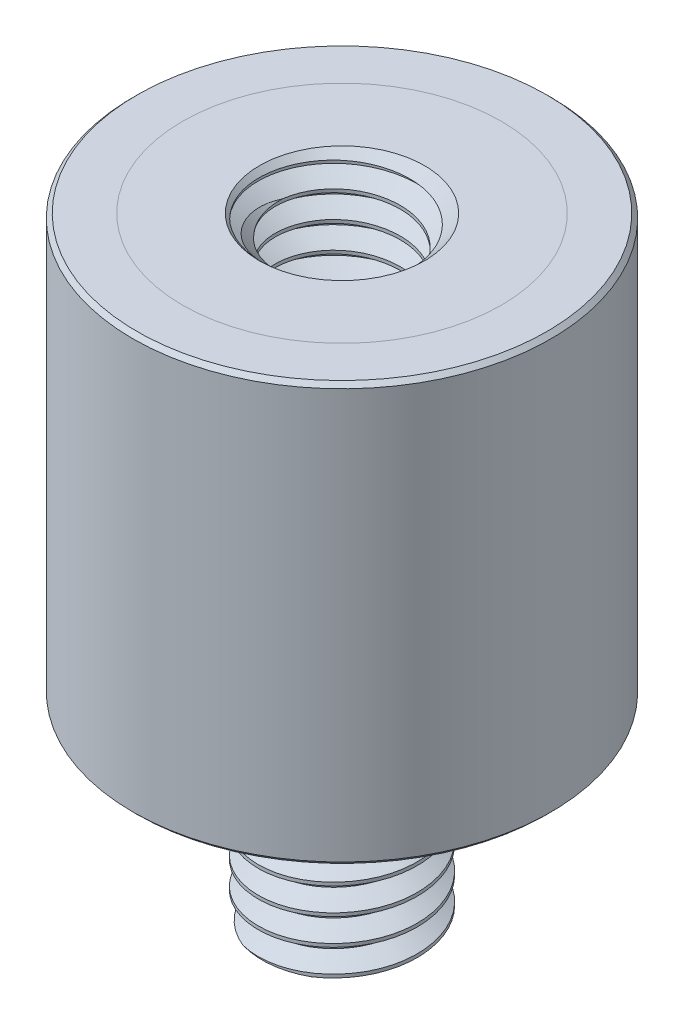
SolidWorks part; units mm, degrees
ref_plane "Front Plane" through (0, 0, 0) normal (0, 0, 1) x (1, 0, 0)
ref_plane "Top Plane" through (0, 0, 0) normal (0, 1, 0) x (1, 0, 0)
ref_plane "Right Plane" through (0, 0, 0) normal (1, 0, 0) x (0, 0, -1)
sketch "Sketch1" plane through (0, 0, 0) normal (1, 0, 0) x (0, 0, -1)
  line L0 (0, 0) -> (0, -6.096) construction
  line L1 (-3.937, 7.874) -> (3.937, 7.874) construction
  line L2 (-3.937, 7.874) -> (-3.937, 0) construction
  line L3 (-3.937, 0) -> (3.937, 0) construction
  line L4 (3.937, 7.874) -> (3.937, 0) construction
  line L5 (-1.5, -6.096) -> (1.5, -6.096) construction
  line L6 (-1.5, 7.874) -> (-1.5, 4.826) construction
  line L7 (-1.5, 4.826) -> (1.5, 4.826) construction
  line L8 (1.5, 4.826) -> (1.5, 7.874) construction
  line L9 (-1.5541, -6.0648) -> (-1.5541, -6.5648) construction
  line L10 (-1.5541, -6.5648) -> (-1.1211, -6.3148) construction
  line L11 (-1.1211, -6.3148) -> (-1.5541, -6.0648) construction
  line L12 (-1.5271, -6.0804) -> (-1.5271, -6.5491) construction
  line L13 (-1.5, -6.096) -> (-1.5, -6.5335) construction
  line L14 (-1.1752, -6.2835) -> (-1.1752, -6.346) construction
  line L15 (-1.1752, -6.3148) -> (-1.1211, -6.3148) construction
  line L16 (-1.5541, -6.3148) -> (-1.5, -6.3148) construction
  line L17 (-1.5541, 8.3427) -> (-1.5541, 7.8428) construction
  line L18 (-1.5541, 7.8428) -> (-1.1211, 8.0927) construction
  line L19 (-1.1211, 8.0927) -> (-1.5541, 8.3427) construction
  line L20 (-1.5271, 8.3271) -> (-1.5271, 7.8584) construction
  line L21 (-1.5, 8.3115) -> (-1.5, 7.874) construction
  line L22 (-1.1752, 8.124) -> (-1.1752, 8.0615) construction
  line L23 (-1.1752, 8.0927) -> (-1.1211, 8.0927) construction
  line L24 (-1.5541, 8.0927) -> (-1.5, 8.0927) construction
  point P4 (0, 0)
  point P11 (0, -6.096)
  point P14 (0, 4.826)
  point P28 (-1.5271, -6.3148)
  point P29 (3.937, 1.016)
  point P41 (-1.5271, 8.0927)
  point P42 (-3, 0)
  point P43 (3, 0)
  point P44 (1.5, -4.346)
  point P46 (1.5, 7.874)
  point P47 (3.937, 6.858)
  dimension "Thread OD" = 3
  dimension "Diameter" = 7.874
  dimension "Height" = 7.874
  dimension "Thread length" = 6.096
  dimension "Thread depth" = 3.048
  dimension "D1" = 3
  dimension "D2" = 60
  dimension "Thread Pitch" = 0.5
  dimension "D3" = 0.0625
  dimension "D4" = 0.5
  dimension "D5" = 0.0625
  dimension "D6" = 60
  dimension "Cover Plate Thickness" = 1.016
  dimension "D8" = 1.016
  dimension "Cover Plate Diameter" = 6
  dimension "D10" = 1.75
sketch "Sketch2" plane through (0, 0, 0) normal (0, 1, 0) x (1, 0, 0)
  circle A0 centre (0, 0) radius 3.937 construction
  dimension "D1" = 7.874
sketch "Sketch3" plane through (0, 0, 0) normal (1, 0, 0) x (0, 0, -1)
  line L0 (0, 1.016) -> (0, -6.096)
  line L1 (0, -6.096) -> (-1.15, -6.096)
  line L2 (-1.5, -6.096) -> (1.5, -6.096) construction
  line L3 (-1.15, -6.096) -> (-1.5, -5.746)
  line L4 (-1.5, -5.746) -> (-1.5, 1.016)
  line L5 (-1.5, 1.016) -> (0, 1.016)
  dimension "D1" = 45
  dimension "D2" = 0.35
revolve "Revolve1" add sketch "Sketch3" angle 360 about L0
sketch "Sketch4" plane through (0, 0, 0) normal (1, 0, 0) x (0, 0, -1)
  line L1 (-1.875, 6.858) -> (-1.875, 3.951)
  line L5 (-3, 7.874) -> (-3, 6.858)
  line L6 (-1.5, 7.874) -> (-1.5, 4.826)
  line L7 (-3.937, 7.874) -> (3.937, 7.874) construction
  line L8 (-1.5, 4.826) -> (0, 4.326)
  line L9 (-3, 6.858) -> (-1.875, 6.858)
  line L11 (-3, 7.874) -> (-1.5, 7.874)
  line L13 (0, 7.874) -> (0, 4.826) construction
  line L14 (-1.5, 4.826) -> (1.5, 4.826) construction
  line L15 (0, 4.826) -> (0, 4.326) construction
  line L16 (0, 4.326) -> (0, 3.951)
  line L17 (0, 3.951) -> (-1.875, 3.951)
  line L18 (-1.875, 6.858) -> (-1.5, 6.858) construction
  dimension "D1" = 0.5
  dimension "D2" = 3.75
revolve "Revolve2" add sketch "Sketch4" angle 360 about L13
sketch "Sketch5" plane through (0, 0, 0) normal (1, 0, 0) x (0, 0, -1)
  line L0 (-3, 0) -> (-3, 1.016)
  line L1 (-3, 1.016) -> (-1.5, 1.016)
  line L2 (-1.5, 1.016) -> (-1.5, 0)
  line L3 (-3.937, 0) -> (3.937, 0) construction
  line L4 (-1.5, 0) -> (-3, 0)
revolve "Revolve3" add sketch "Sketch5" angle 360 about L0
sketch "Sketch6" plane through (0, 0, 0) normal (1, 0, 0) x (0, 0, -1)
  line L0 (-3, 7.874) -> (-3.937, 7.874)
  line L1 (-3.937, 7.874) -> (-3.937, 0)
  line L2 (-3.937, 0) -> (-3, 0)
  line L3 (-3, 0) -> (-3, 1.016)
  line L4 (-3, 1.016) -> (0, 1.016)
  line L5 (0, 1.016) -> (0, 3.951)
  line L6 (0, 3.951) -> (-1.875, 3.951)
  line L7 (-1.875, 3.951) -> (-1.875, 6.858)
  line L8 (-1.875, 6.858) -> (-3, 6.858)
  line L9 (-3, 6.858) -> (-3, 7.874)
revolve "Revolve4" add sketch "Sketch6" angle 360 about L5
chamfer "Chamfer1" distance 0.0787 2 edges at (0, 7.874, -3.937) (0, 0, -3.937)
split "Split1" bodies to split 106 resulting bodies 108 109 split by face at (0, 0, -1.5)
sketch "Sketch7" plane through (0, 0, 0) normal (1, 0, 0) x (0, 0, -1)
  line L0 (-1.5271, -6.0804) -> (-1.5271, -6.5491)
  line L1 (-1.5271, -6.5491) -> (-1.1752, -6.346)
  line L2 (-1.1752, -6.346) -> (-1.1752, -6.2835)
  line L3 (-1.1752, -6.2835) -> (-1.5271, -6.0804)
sketch "Sketch8" plane through (0, -6.096, 0) normal (0, -1, 0) x (1, 0, 0)
  line L0 (0, 1.5) -> (0, -1.5) construction
  circle A0 centre (0, 0) radius 1.5
curve "Helix/Spiral1" pitch 0.5 height 6.596 radius 1.5 centre (0, -6.096, 0) axis (0, 1, 0) start towards (0, 0, 1)
sweep "Cut-Sweep1" cut profiles "Sketch7" path "Helix/Spiral1" align with end faces yes
combine bodies "Combine1" operation type add bodies to combine 109 110
sketch "Sketch9" plane through (0, 0, 0) normal (1, 0, 0) x (0, 0, -1)
  line L0 (-1.5271, 8.3271) -> (-1.5271, 7.8584)
  line L1 (-1.5271, 8.3271) -> (-1.1752, 8.124)
  line L2 (-1.1752, 8.124) -> (-1.1752, 8.0615)
  line L3 (-1.1752, 8.0615) -> (-1.5271, 7.8584)
sketch "Sketch10" plane through (0, 7.874, 0) normal (0, 1, 0) x (1, 0, 0)
  line L0 (0, -3.937) -> (0, 3.937) construction
  circle A0 centre (0, 0) radius 1.5
curve "Helix/Spiral2" pitch 0.5 height 3.548 radius 1.5 centre (0, 7.874, 0) axis (0, -1, 0) start towards (0, 0, 1)
sweep "Sweep1" add profiles "Sketch9" path "Helix/Spiral2"
sketch "Sketch11" plane through (0, 7.874, 0) normal (0, 1, 0) x (1, 0, 0)
  line L0 (0, -3.937) -> (0, 3.937) construction
  circle A0 centre (0, 0) radius 1.5541
extrude "Cut-Extrude1" cut sketch "Sketch11" along normal through all and the other way through all draft 45
sketch "Sketch12" plane through (0, -6.096, 0) normal (0, -1, 0) x (1, 0, 0)
  circle A0 centre (0, 0) radius 1.831
extrude "Cut-Extrude2" cut sketch "Sketch12" against normal blind 2.54
equation "\"D1@Sketch1\"=\"Thread OD@Sketch1\""
equation "\"D1@Sketch2\"=\"Diameter@Sketch1\""
equation "\"D3@Sketch1\"=\"Thread Pitch@Sketch1\"/8"
equation "\"D4@Sketch1\"=\"Thread Pitch@Sketch1\""
equation "\"D5@Sketch1\"=\"D4@Sketch1\"/8"
equation "\"D8@Sketch1\"=\"Cover Plate Thickness@Sketch1\""
equation "\"D2@Sketch3\"=\"Thread Pitch@Sketch1\"*.7"
equation "\"D1@Sketch4\"=\"D4@Sketch1\""
equation "\"D2@Sketch4\"=\"D1@Sketch1\"*1.25"
equation "\"D4@Helix/Spiral1\"=\"Thread Pitch@Sketch1\""
equation "\"D3@Helix/Spiral1\"=\"Thread length@Sketch1\"+\"Thread Pitch@Sketch1\""
equation "\"D3@Helix/Spiral2\"=\"Thread depth@Sketch1\"+\"D4@Sketch1\""
equation "\"D4@Helix/Spiral2\"=\"D4@Sketch1\""
equation "\"D10@Sketch1\"=\"Thread Pitch@Sketch1\"*3.5"
equation "\"D1@Chamfer1\"=\"Height@Sketch1\"*.01"
